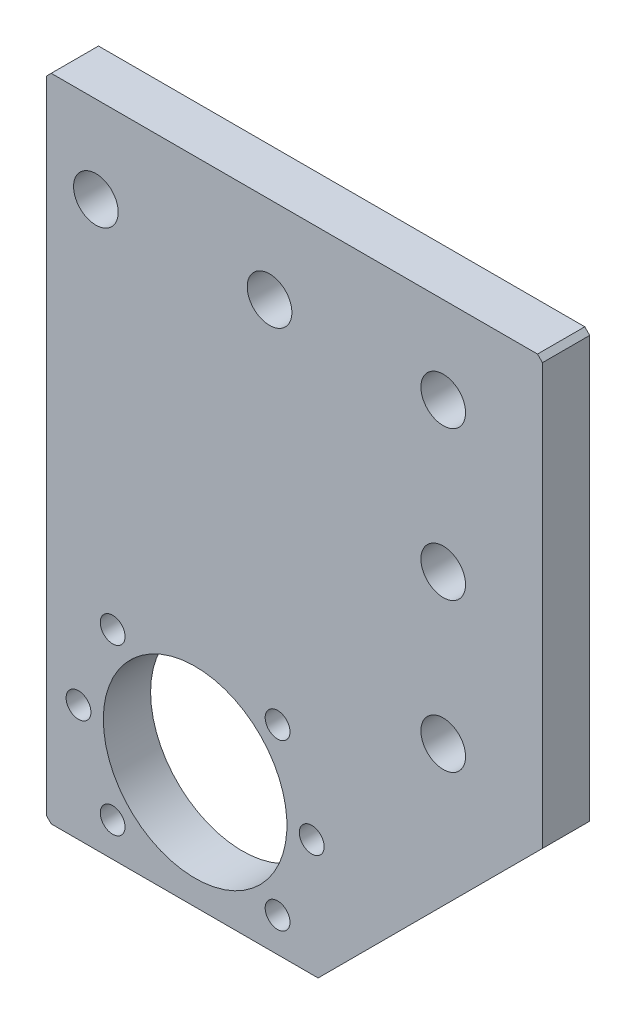
SolidWorks part; units mm, degrees
material "6061-T6 (SS)"
ref_plane "Front Plane" through (0, 0, 0) normal (0, 0, 1) x (1, 0, 0)
ref_plane "Top Plane" through (0, 0, 0) normal (0, 1, 0) x (1, 0, 0)
ref_plane "Right Plane" through (0, 0, 0) normal (1, 0, 0) x (0, 0, -1)
sketch "Sketch1" plane through (0, 0, 0) normal (0, 0, 1) x (1, 0, 0)
  line L0 (-20, 90) -> (15, 90) construction
  line L1 (-30, -23.5) -> (24.7843, -23.5)
  line L2 (-30, -23.5) -> (-30, 107.5)
  line L3 (-30, 107.5) -> (70, 107.5)
  line L4 (70, 21.7157) -> (70, 107.5)
  line L5 (15, 90) -> (50, 90) construction
  line L6 (50, 90) -> (50, 60) construction
  line L7 (50, 60) -> (50, 30) construction
  line L8 (0, -55) -> (0, 55) construction
  line L9 (0, 23.5) -> (-16.617, 16.617) construction
  line L10 (-16.617, 16.617) -> (-23.5, 0) construction
  line L11 (-23.5, 0) -> (-16.617, -16.617) construction
  line L12 (-16.617, -16.617) -> (0, -23.5) construction
  line L13 (0, -23.5) -> (16.617, -16.617) construction
  line L14 (16.617, -16.617) -> (23.5, 0) construction
  line L15 (23.5, 0) -> (16.617, 16.617) construction
  line L16 (16.617, 16.617) -> (0, 23.5) construction
  line L17 (24.7843, -23.5) -> (70, 21.7157)
  circle A0 centre (0, 0) radius 18.5
  circle A1 centre (0, 0) radius 21.7112 construction
  circle A2 centre (50, 30) radius 20 construction
  dimension "D1" = 37
  dimension "D2" = 30
  dimension "D3" = 23.5
  dimension "D4" = 17.5
  dimension "D5" = 70
  dimension "D6" = 30
  dimension "D7" = 10
  dimension "D8" = 20
  dimension "D9" = 90
  dimension "D10" = 47
  dimension "D11" = 35
  dimension "D12" = 45
extrude "Boss-Extrude1" add sketch "Sketch1" along normal mid plane 9.525
hole_wizard "M8 Clearance Hole1" positions "Sketch2" profile "Sketch3" hole size "M8" standard "ANSI Metric" end condition up to next
sketch "Sketch2" plane through (0, 0, 4.7625) normal (0, 0, 1) x (1, 0, 0)
  point P0 (-20, 90)
  point P3 (15, 90)
  point P6 (50, 90)
  point P9 (50, 60)
  point P12 (50, 30)
sketch "Sketch3" plane through (-20, 90, 4.7625) normal (1, 0, 0) x (0, -1, 0)
  line L0 (0, 0) -> (0, 9.525)
  line L1 (0, 9.525) -> (4.5, 9.525)
  line L2 (4.5, 9.525) -> (4.5, 0)
  line L5 (4.5, 0) -> (0, 0)
  line L11 (0, -6.35) -> (0, 107.95) construction
  dimension "Thru Hole Dia." = 9
  dimension "Thru Hole Depth" = 9.525
hole_wizard "M6x1.0 Tapped Hole1" positions "Sketch4" profile "Sketch5" tap size "M6x1.0" standard "ANSI Metric" end condition up to next
sketch "Sketch4" plane through (0, 0, 4.7625) normal (0, 0, 1) x (1, 0, 0)
  point P3 (16.617, 16.617)
  point P6 (23.5, 0)
  point P9 (16.617, -16.617)
  point P12 (-16.617, -16.617)
  point P15 (-23.5, 0)
  point P18 (-16.617, 16.617)
sketch "Sketch5" plane through (16.617, 16.617, 4.7625) normal (1, 0, 0) x (0, -1, 0)
  line L0 (0, 0) -> (0, 9.525)
  line L1 (0, 9.525) -> (2.5, 9.525)
  line L2 (2.5, 9.525) -> (2.5, 0)
  line L5 (2.5, 0) -> (0, 0)
  line L11 (0, -6.35) -> (0, 107.95) construction
  dimension "Thru Tap Drill Dia." = 5
  dimension "Thru Tap Drill Depth" = 9.525
cosmetic thread "Hole Thread1" parameters "D2"=6
cosmetic thread "Hole Thread2" parameters "D2"=6
cosmetic thread "Hole Thread3" parameters "D2"=6
cosmetic thread "Hole Thread4" parameters "D2"=6
cosmetic thread "Hole Thread5" parameters "D2"=6
cosmetic thread "Hole Thread6" parameters "D2"=6
chamfer "Chamfer1" distance 1 3 edges at (-30, -23.5, 0) (70, 107.5, 0) (-30, 107.5, 0)
